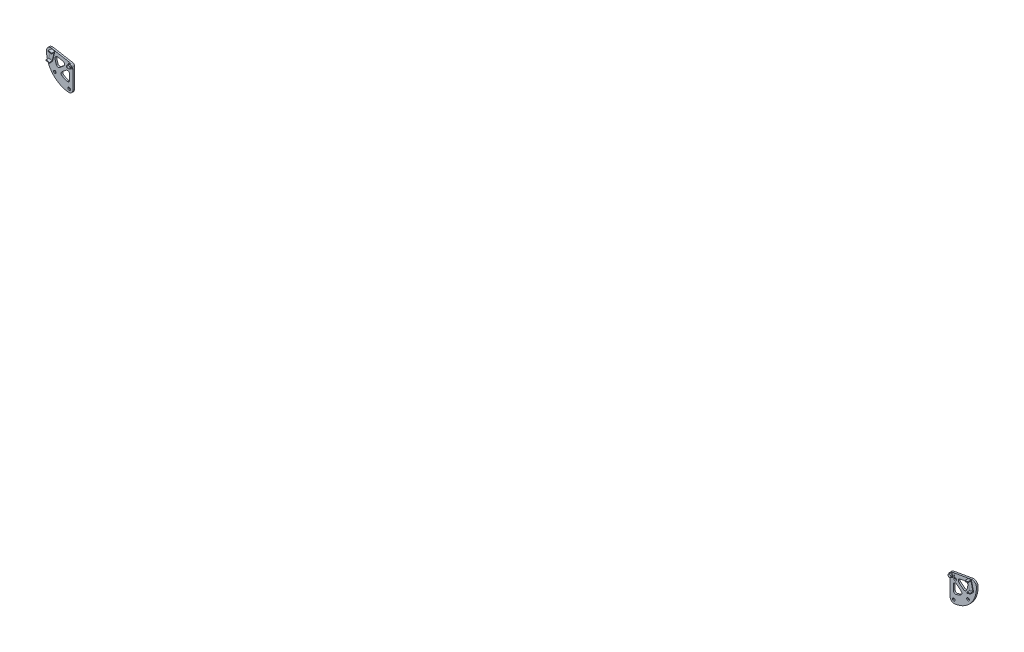
SolidWorks part; units mm, degrees
ref_plane "Front Plane" through (0, 0, 0) normal (0, 0, 1) x (1, 0, 0)
ref_plane "Top Plane" through (0, 0, 0) normal (0, 1, 0) x (1, 0, 0)
ref_plane "Right Plane" through (0, 0, 0) normal (1, 0, 0) x (0, 0, -1)
sketch "Sketch1" plane through (0, 0, 0) normal (0, 0, 1) x (1, 0, 0)
  circle A0 centre (0, 0) radius 45 construction
  dimension "D1" = 90
sketch "Sketch2" plane through (0, 0, 0) normal (0, 0, 1) x (1, 0, 0)
  circle A0 centre (0, 0) radius 3.5
  dimension "D1" = 7
extrude "Boss-Extrude1" add sketch "Sketch2" along normal mid plane 3
sketch "Sketch3" plane through (0, 0, -1.5) normal (0, 0, -1) x (-1, 0, 0)
  circle A0 centre (0, 0) radius 4.5
  dimension "D1" = 9
extrude "Boss-Extrude2" add sketch "Sketch3" along normal blind 3
sketch "Sketch4" plane through (0, 0, -4.5) normal (0, 0, -1) x (-1, 0, 0)
  line L0 (4.5, 0) -> (4.5, -47.6839)
  line L1 (-46.178, 12.7118) -> (0.7814, 4.4316)
  line L2 (0, 0) -> (-44.4306, -37.2817) construction
  line L3 (-3.5, -18.881) -> (-3.5, -31.8865)
  line L4 (-11.7139, -15.0508) -> (-21.75, -23.4721)
  line L5 (-16.8562, -8.9224) -> (-26.8923, -17.3437)
  line L6 (-19.2019, -0.1682) -> (-32.0099, 2.0902)
  line L7 (-37.3186, 7.8706) -> (-46.5707, 10.0269) construction
  line L8 (-51.1101, -9.4511) -> (-40.8842, -11.8344) construction
  line L9 (-37.3186, 7.8706) -> (-46.5707, 10.0269) construction
  line L10 (-51.1101, -9.4511) -> (-40.8842, -11.8344) construction
  line L15 (-40.8842, -11.8344) -> (-40.8842, -11.9511) construction
  circle A0 centre (0, 0) radius 4.5 construction
  arc A1 (-6.6458, -57.618) -> (-57.8967, 3.4604) centre (0, 0) cw
  arc A2 (4.5, 0) -> (0.7814, 4.4316) centre (0, 0) ccw
  arc A3 (4.5, -47.6839) -> (-6.6458, -57.618) centre (-5.5, -47.6839) cw
  arc A4 (-57.8967, 3.4604) -> (-46.178, 12.7118) centre (-47.9145, 2.8638) cw
  arc A5 (-21.3446, -31.439) -> (-9.7879, -36.7178) centre (0, 0) ccw
  arc A6 (-21.75, -23.4721) -> (-21.3446, -31.439) centre (-18.5361, -27.3023) ccw
  arc A7 (-9.7879, -36.7178) -> (-3.5, -31.8865) centre (-8.5, -31.8865) ccw
  arc A8 (-3.5, -18.881) -> (-11.7139, -15.0508) centre (-8.5, -18.881) ccw
  arc A9 (-19.2019, -0.1682) -> (-16.8562, -8.9224) centre (-20.0702, -5.0922) cw
  arc A10 (-37.8596, -3.2632) -> (-32.0099, 2.0902) centre (-32.8781, -2.8338) cw
  arc A11 (-26.8923, -17.3437) -> (-34.6678, -15.561) centre (-30.1062, -13.5135) cw
  arc A12 (-34.6678, -15.561) -> (-37.8596, -3.2632) centre (0, 0) cw
  circle A13 centre (-46.9481, -5.0304) radius 1.25 construction
  circle A14 centre (-44.7919, 4.2216) radius 1.25 construction
  circle A15 centre (-46.9481, -5.0304) radius 1.25 construction
  circle A16 centre (-44.7919, 4.2216) radius 1.25 construction
  point P21 (0, 0)
  circle M1 centre (0, 0) radius 4.5
  dimension "D2" = 38
  dimension "D3" = 10
  dimension "D6" = 58
  dimension "D7" = 5
  dimension "D1" = 100
  dimension "D4" = 8
  dimension "D5" = 4
extrude "Boss-Extrude4" add sketch "Sketch4" along normal blind 4 contours M1 | A1 L0 L1 M1 | L2 L1 A4 A1 A11 A12 A10 L6 A9 L5 M1 region at (0, 0, -4.5) region at (25.4949, -21.3927, -4.5)
sketch "Sketch5" plane through (0, 0, -4.5) normal (0, 0, 1) x (1, 0, 0)
  line L0 (37.3186, 7.8706) -> (46.5707, 10.0269) construction
  line L1 (38.7795, 8.2111) -> (46.5707, 10.0269)
  line L2 (51.1101, -9.4511) -> (40.8842, -11.8344) construction
  line L3 (51.1101, -9.4511) -> (40.8842, -11.8344) construction
  line L5 (43.3189, -11.2669) -> (51.1101, -9.4511)
  line L6 (51.1101, -9.4511) -> (46.5707, 10.0269)
  line L7 (38.7795, 8.2111) -> (43.3189, -11.2669)
  dimension "D1" = 8
extrude "Boss-Extrude5" add sketch "Sketch5" along normal up to surface (1.25 mm away)
sketch "Sketch6" plane through (0, 0, -4.5) normal (0, 0, 1) x (1, 0, 0)
  line L0 (38.7795, 8.2111) -> (46.5707, 10.0269)
  line L2 (38.7795, 8.2111) -> (38.3255, 10.1589)
  line L3 (46.5707, 10.0269) -> (46.1167, 11.9747)
  line L4 (38.3255, 10.1589) -> (46.1167, 11.9747)
  line L5 (46.5707, 10.0269) -> (51.1101, -9.4511) construction
  line L6 (48.8404, 0.2879) -> (34.6145, -3.0276) construction
  line L7 (51.1101, -9.4511) -> (51.5641, -11.3989)
  line L8 (43.3189, -11.2669) -> (51.1101, -9.4511)
  line L9 (43.3189, -11.2669) -> (43.7729, -13.2147)
  line L10 (43.7729, -13.2147) -> (51.5641, -11.3989)
  dimension "D1" = 2
extrude "Boss-Extrude6" add sketch "Sketch6" along normal up to surface (7.75 mm away)
hole_wizard "CSK for M3 Flat Head Machine Screw1" positions "Sketch12" profile "Sketch11" countersink size "M3" standard "ANSI Metric" end condition through all
sketch "Sketch12" plane through (0, 0, -4.5) normal (0, 0, 1) x (1, 0, 0)
  line L0 (7.6604, -6.4279) -> (38.3022, -32.1394) construction
  line L2 (26.8923, -17.3437) -> (21.75, -23.4721) construction
  line L4 (26.8923, -17.3437) -> (24.3212, -20.4079)
  line L6 (0, 0) -> (4.3578, -49.8097) construction
  point P0 (4.3578, -49.8097)
  point P2 (38.3022, -32.1394)
  point P4 (7.6604, -6.4279)
  dimension "D1" = 10
  dimension "D2" = 50
  dimension "D3" = 50
  dimension "D4" = 45
sketch "Sketch11" plane through (4.3578, -49.8097, -4.5) normal (1, 0, 0) x (0, -1, 0)
  line L0 (0, 0) -> (0, 4)
  line L1 (0, 4) -> (1.7, 4)
  line L2 (1.7, 4) -> (1.7, 1.45)
  line L3 (1.7, 1.45) -> (3.15, 0)
  line L5 (3.15, 0) -> (0, 0)
  line L6 (-1.7, 1.45) -> (-3.15, 0) construction
  line L11 (0, -6.35) -> (0, 107.95) construction
  dimension "Thru Hole Dia." = 3.4
  dimension "Thru Hole Depth" = 4
  dimension "Near C'Sink Dia." = 6.3
  dimension "Near C'Sink Angle" = 90
fillet "Fillet1" radius 2 1 edges
ref_plane "Plane1" through (-1045.0612, 0, 0) normal (1, 0, 0) x (0, 0, -1)
mirror "Mirror4" about plane through (-1045.0612, 0, 0) normal (1, 0, 0) of bodies 109
